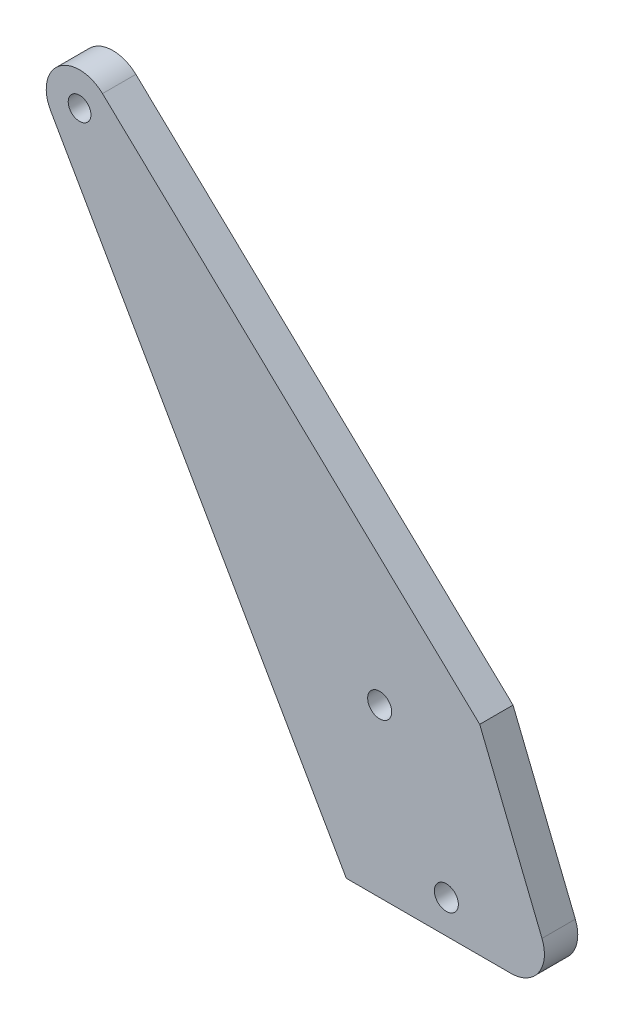
SolidWorks part; units mm, degrees
ref_plane "Front Plane" through (0, 0, 0) normal (0, 0, 1) x (1, 0, 0)
ref_plane "Top Plane" through (0, 0, 0) normal (0, 1, 0) x (1, 0, 0)
ref_plane "Right Plane" through (0, 0, 0) normal (1, 0, 0) x (0, 0, -1)
sketch "Sketch1" plane through (0, 0, 0) normal (0, 0, 1) x (1, 0, 0)
  line L1 (0, 0) -> (-25.4, 0)
  line L6 (-71.8309, 106.208) -> (0, 38.1)
  line L7 (-81.712, 98.4471) -> (-25.4, 0)
  line L8 (-323.85, -215.9) -> (44.45, -215.9) construction
  line L9 (0, 38.1) -> (15.3934, 0)
  line L10 (15.3934, 0) -> (0, 0)
  line L11 (0, 38.1) -> (0, 0) construction
  arc A1 (-71.8309, 106.208) -> (-81.712, 98.4471) centre (-76.2, 101.6) ccw
  circle A2 centre (-6.35, 6.35) radius 2.286
  circle A3 centre (-19.05, 31.75) radius 2.286
  circle A4 centre (-76.2, 101.6) radius 2.159
  point P5 (-63.5, 133.35)
  point P7 (23.3733, 0)
  dimension "D3" = 76.2
  dimension "D5" = 12.7
  dimension "D7" = 4.572
  dimension "D4" = 6.35
  dimension ".17" = 4.318
  dimension "D1" = 25.4
  dimension "D2" = 38.1
  dimension "D6" = 317.5
  dimension "D8" = 31.75
  dimension "D9" = 19.05
  dimension "D11" = 6.35
  dimension "D12" = 22
extrude "Boss-Extrude1" add sketch "Sketch1" against normal blind 6.35
fillet "Fillet1" radius 6.35 1 edges at (15.3934, 0, -3.175)
sketch "Sketch3" plane through (0, 0, 0) normal (0, 0, 1) x (1, 0, 0)
  line L0 (-76.2, 101.6) -> (-180.5328, -115.6414) construction
  line L1 (-13.2351, 71.3603) -> (-117.5679, -145.881)
  line L2 (-139.1649, 131.8397) -> (-243.4978, -85.4017)
  arc A0 (-13.2351, 71.3603) -> (-139.1649, 131.8397) centre (-76.2, 101.6) ccw
  arc A1 (-243.4978, -85.4017) -> (-117.5679, -145.881) centre (-180.5328, -115.6414) ccw
  point P3 (-186.0722, -120.3802)
  point P4 (-128.3664, -7.0207)
  point P9 (-137.8247, -108.4712)
  point P10 (-154.1866, -108.4712)
  point P11 (-166.7022, -109.502)
  point P12 (-166.0785, -118.8573)
  point P13 (0, 0)
  point P14 (-165.336, -111.4933)
  point P15 (-190.0015, -134.3848)
  point P16 (-180.5328, -115.6414)
  dimension "D1" = 139.7
